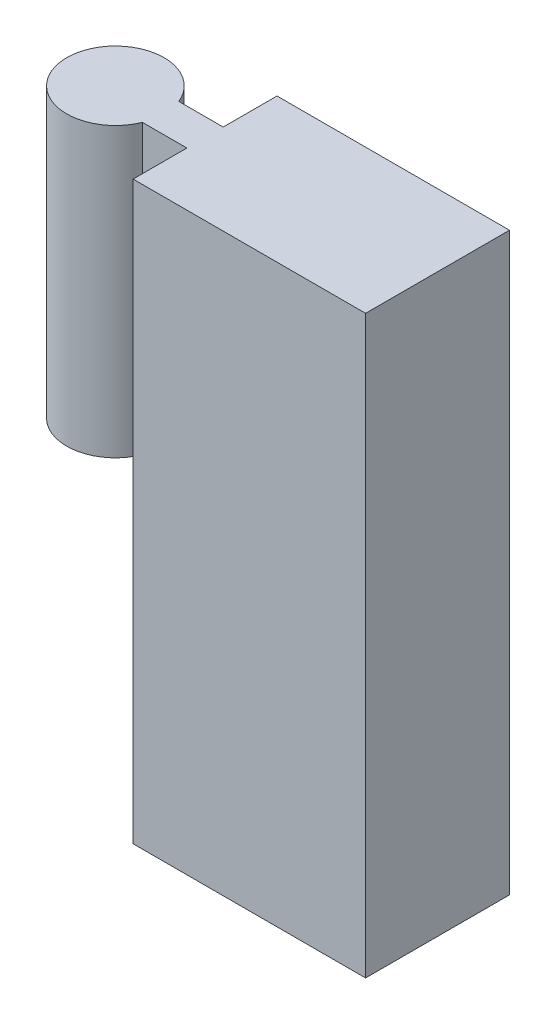
SolidWorks part; units mm, degrees
ref_plane "Płaszczyzna przednia" through (0, 0, 0) normal (0, 0, 1) x (1, 0, 0)
ref_plane "Płaszczyzna górna" through (0, 0, 0) normal (0, 1, 0) x (1, 0, 0)
ref_plane "Płaszczyzna prawa" through (0, 0, 0) normal (1, 0, 0) x (0, 0, -1)
sketch "Szkic1" plane through (0, 0, 0) normal (0, 0, 1) x (1, 0, 0)
  line L1 (-5.25, 13) -> (5.25, 13)
  line L2 (-5.25, 13) -> (-5.25, -13)
  line L3 (-5.25, -13) -> (5.25, -13)
  line L4 (5.25, 13) -> (5.25, -13)
  line L5 (-5.25, 13) -> (5.25, -13) construction
  line L6 (-5.25, -13) -> (5.25, 13) construction
  point P0 (0, 0)
  dimension "D1" = 10.5
  dimension "D2" = 26
extrude "Dodanie-wyciągnięcie1" add sketch "Szkic1" along normal blind 6.5
sketch "Szkic3" plane through (0, 13, 0) normal (0, 1, 0) x (1, 0, 0)
  line L0 (-5.25, -3.25) -> (-9.3, -3.25) construction
  line L1 (-5.25, -6.5) -> (-5.25, 0) construction
  line L3 (-5.25, -4.0704) -> (-9.3, -4.0704)
  line L4 (-5.25, -4.0704) -> (-5.25, -2.4296)
  line L5 (-5.25, -2.4296) -> (-9.3, -2.4296)
  line L6 (-9.3, -4.0704) -> (-9.3, -2.4296)
  line L7 (-5.25, -4.0704) -> (-9.3, -2.4296) construction
  line L8 (-5.25, -2.4296) -> (-9.3, -4.0704) construction
  circle A0 centre (-9.3, -3.25) radius 2.2
  point P5 (-7.275, -3.25)
  line M10 (-5.25, 0) -> (-5.25, -6.5)
  dimension "D2" = 4.4
  dimension "D1" = 4.05
extrude "Dodanie-wyciągnięcie2" add sketch "Szkic3" against normal blind 13 contours L5 A0 L3 L6 | L3 A0 L5 L6 | A0 L3 L5 M10 region at (-6.2016, 13, 3.25) region at (-9.6242, 13, 3.25) region at (-8.2255, 13, 3.25)
